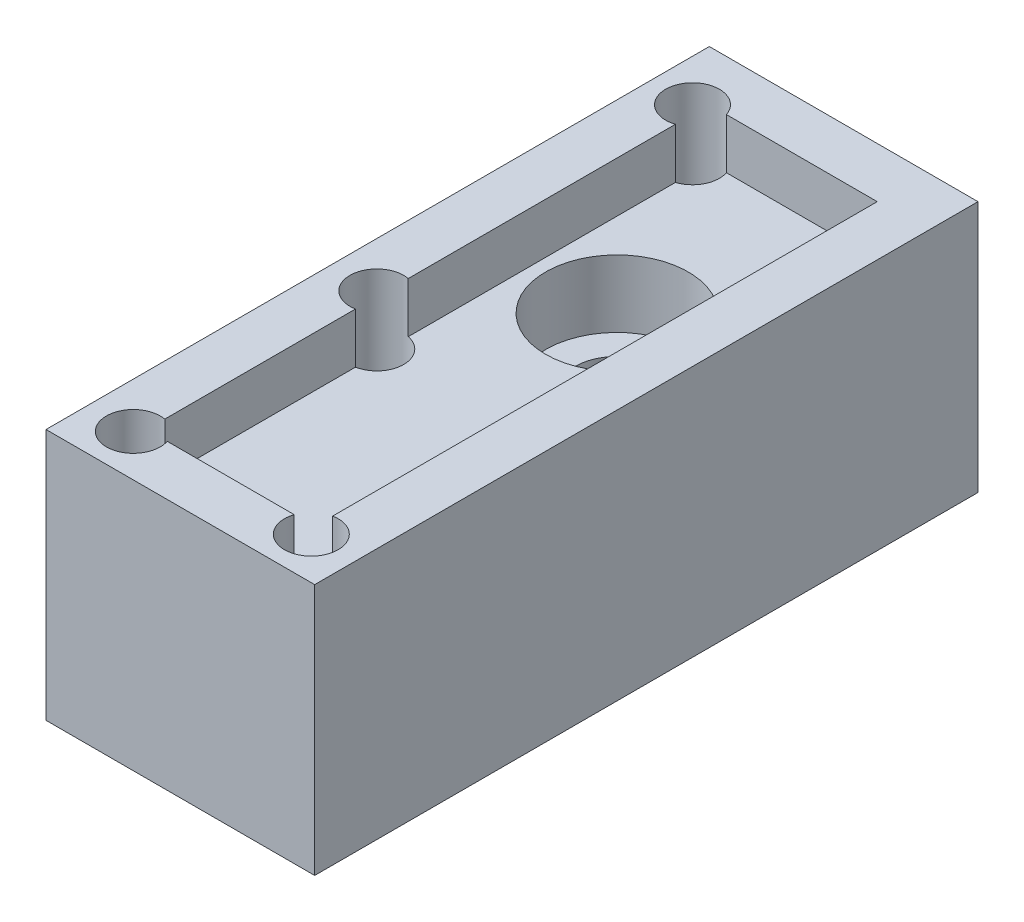
SolidWorks part; units mm, degrees
ref_plane "Front Plane" through (0, 0, 0) normal (0, 0, 1) x (1, 0, 0)
ref_plane "Top Plane" through (0, 0, 0) normal (0, 1, 0) x (1, 0, 0)
ref_plane "Right Plane" through (0, 0, 0) normal (1, 0, 0) x (0, 0, -1)
sketch "Sketch1" plane through (0, 0, 0) normal (0, 1, 0) x (1, 0, 0)
  line L1 (0, 0) -> (16, 0)
  line L2 (0, 0) -> (0, 39.5)
  line L3 (0, 39.5) -> (16, 39.5)
  line L4 (16, 0) -> (16, 39.5)
extrude "Boss-Extrude1" add sketch "Sketch1" along normal blind 15
sketch "Sketch2" plane through (0, 15, 0) normal (0, 1, 0) x (1, 0, 0)
  line L1 (3, 3) -> (13, 3)
  line L2 (3, 3) -> (3, 36.5)
  line L3 (3, 36.5) -> (13, 36.5)
  line L4 (13, 3) -> (13, 36.5)
extrude "Cut-Extrude1" cut sketch "Sketch2" against normal blind 3
sketch "Sketch3" plane through (0, 12, 0) normal (0, 1, 0) x (1, 0, 0)
  circle A0 centre (2.7, 2.5) radius 1.6
extrude "Cut-Extrude2" cut sketch "Sketch3" against normal through all and the other way through all
sketch "Sketch4" plane through (0, 15, 0) normal (0, 1, 0) x (1, 0, 0)
  circle A0 centre (13.3, 2.5) radius 1.6
  circle A1 centre (2.7, 17) radius 1.6
  circle A2 centre (2.5, 36) radius 1.6
extrude "Cut-Extrude3" cut sketch "Sketch4" against normal through all and the other way blind 3
sketch "Sketch5" plane through (0, 12, 0) normal (0, 1, 0) x (1, 0, 0)
  circle A0 centre (8, 26) radius 2.5
sketch "Sketch8" plane through (0, 12, 0) normal (0, 1, 0) x (1, 0, 0)
  circle A0 centre (8, 26) radius 4.25
extrude "Cut-Extrude4" cut sketch "Sketch5" against normal blind 20
extrude "Cut-Extrude5" cut sketch "Sketch8" against normal blind 4 contours A0
